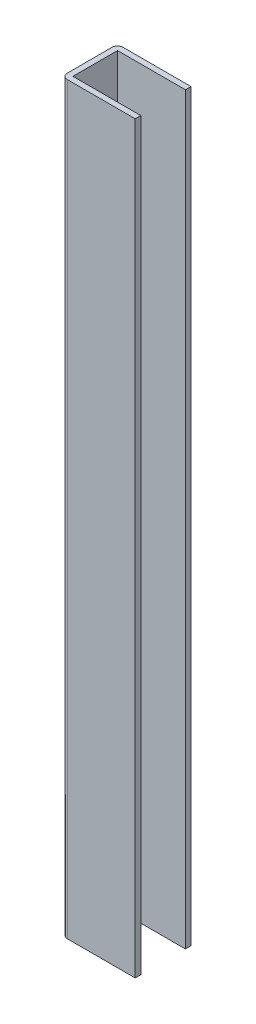
SolidWorks part; units mm, degrees
ref_plane "Спереди" through (0, 0, 0) normal (0, 0, 1) x (1, 0, 0)
ref_plane "Сверху" through (0, 0, 0) normal (0, 1, 0) x (1, 0, 0)
ref_plane "Справа" through (0, 0, 0) normal (1, 0, 0) x (0, 0, -1)
sketch "Эскиз1" plane through (0, 0, 0) normal (0, 1, 0) x (1, 0, 0)
  line L1 (-37, 15) -> (37, 15)
  line L2 (-40, 12) -> (-40, -12)
  line L3 (-37, -15) -> (37, -15)
  line L4 (40, 12) -> (40, -12)
  line L5 (-40, 15) -> (40, -15) construction
  line L6 (-40, -15) -> (40, 15) construction
  arc A0 (-37, 15) -> (-40, 12) centre (-37, 12) ccw
  arc A1 (-40, -12) -> (-37, -15) centre (-37, -12) ccw
  arc A2 (37, -15) -> (40, -12) centre (37, -12) ccw
  arc A3 (37, 15) -> (40, 12) centre (37, 12) cw
  point P0 (0, 0)
  dimension "D1" = 3
extrude "Вытянуть-Тонкостенный1" add sketch "Эскиз1" along normal blind 400 thin thin type one direction reverse wall 3
sketch "Эскиз2" plane through (0, 400, 0) normal (0, 1, 0) x (1, 0, 0)
  line L1 (-0.5, -21.5541) -> (41.1465, -21.5541)
  line L2 (-0.5, -21.5541) -> (-0.5, 20.9728)
  line L3 (-0.5, 20.9728) -> (41.1465, 20.9728)
  line L4 (41.1465, -21.5541) -> (41.1465, 20.9728)
extrude "Вырез-Вытянуть1" cut sketch "Эскиз2" against normal through all
